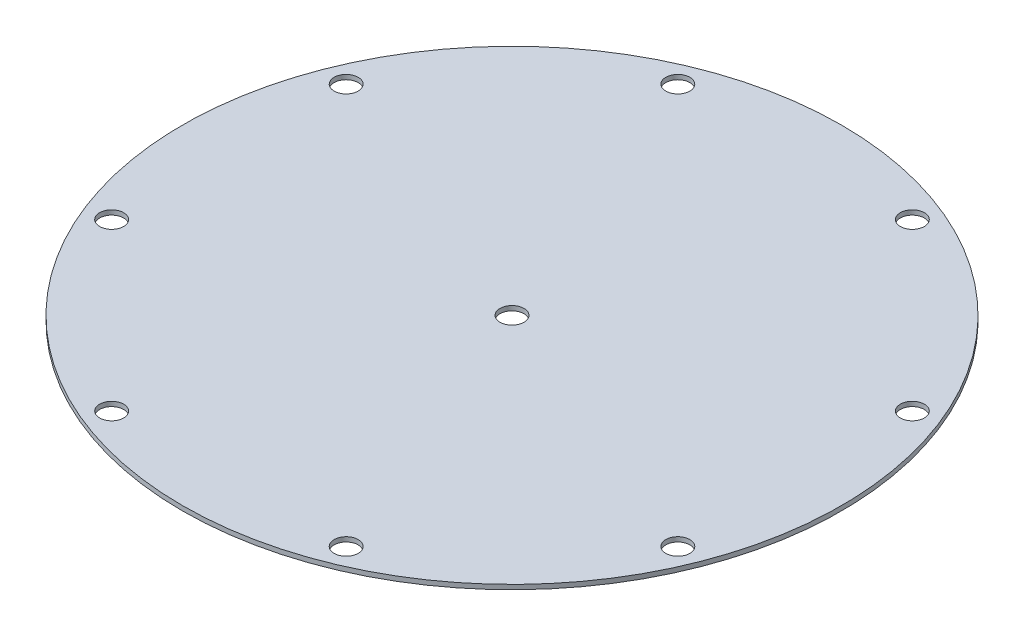
SolidWorks part; units mm, degrees
material "6061-T6 (SS)"
ref_plane "Front Plane" through (0, 0, 0) normal (0, 0, 1) x (1, 0, 0)
ref_plane "Top Plane" through (0, 0, 0) normal (0, 1, 0) x (1, 0, 0)
ref_plane "Right Plane" through (0, 0, 0) normal (1, 0, 0) x (0, 0, -1)
sketch "Sketch2" plane through (0, 0, 0) normal (1, 0, 0) x (0, 0, -1)
  line L0 (0, 0) -> (-71.2, 0)
  line L1 (-71.2, 0) -> (-71.2, 1)
  line L2 (-71.2, 1) -> (0, 1)
  line L5 (0, 1) -> (0, 0)
  dimension "D1" = 71.2
  dimension "D2" = 1
ref_axis "Axis1" through (0, -0.05, 0) along (0, 1, 0)
revolve "Revolve1" add sketch "Sketch2" angle 360 about axis through (0, -0.05, 0) along (0, 1, 0)
hole_wizard "#6 (0.204) Diameter Hole1" positions "Sketch6" profile "Sketch7" hole size "#6" standard "ANSI Inch" end condition through all
sketch "Sketch6" plane through (0, 1, 0) normal (0, 1, 0) x (1, 0, 0)
  line L0 (0, 0) -> (-53.438, 129.0108) construction
  line L2 (0, 0) -> (0, 109.0908) construction
  point P0 (-25.3336, 61.1608)
  dimension "D1" = 22.5
  dimension "D2" = 66.2
sketch "Sketch7" plane through (-25.3336, 1, -61.1608) normal (1, 0, 0) x (0, 0, 1)
  line L0 (0, 0) -> (0, 1)
  line L1 (0, 1) -> (2.5908, 1)
  line L2 (2.5908, 1) -> (2.5908, 0)
  line L5 (2.5908, 0) -> (0, 0)
  line L11 (0, -6.35) -> (0, 107.95) construction
  dimension "Thru Hole Dia." = 5.1816
  dimension "Thru Hole Depth" = 1
pattern_circular "CirPattern3" count 8 over 360 about axis through (0, -0.05, 0) along (0, 1, 0) of "#6 (0.204) Diameter Hole1"
hole_wizard "#6 (0.204) Diameter Hole2" positions "Sketch8" profile "Sketch9" hole size "#6" standard "ANSI Inch" end condition through all
sketch "Sketch8" plane through (0, 1, 0) normal (0, 1, 0) x (1, 0, 0)
  line L0 (0, 0) -> (106.3094, -1.7118) construction
  point P7 (0, 0)
sketch "Sketch9" plane through (0, 1, 0) normal (1, 0, 0) x (0, 0, 1)
  line L0 (0, 0) -> (0, 1)
  line L1 (0, 1) -> (2.5908, 1)
  line L2 (2.5908, 1) -> (2.5908, 0)
  line L5 (2.5908, 0) -> (0, 0)
  line L11 (0, -6.35) -> (0, 107.95) construction
  dimension "Thru Hole Dia." = 5.1816
  dimension "Thru Hole Depth" = 1
equation "\"TubeDiameter\"= 6.000in"
equation "\"D1@Sketch2\"=\"TubeDiameter\"/2-5mm"
equation "\"D2@Sketch6\"=\"TubeDiameter\"/2-10mm"
